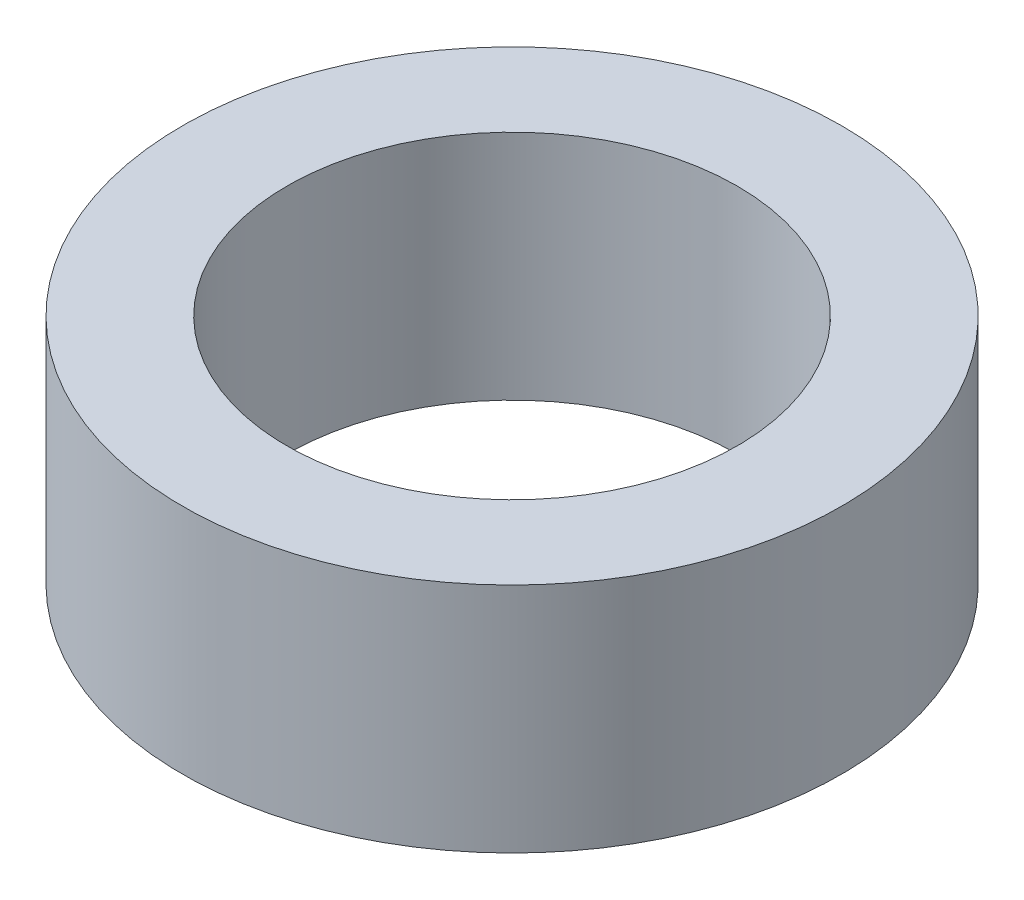
SolidWorks part; units mm, degrees
material "HDPE"
ref_plane "Piano frontale" through (0, 0, 0) normal (0, 0, 1) x (1, 0, 0)
ref_plane "Piano superiore" through (0, 0, 0) normal (0, 1, 0) x (1, 0, 0)
ref_plane "Piano destro" through (0, 0, 0) normal (1, 0, 0) x (0, 0, -1)
sketch "Schizzo1" plane through (0, 0, 0) normal (0, 0, 1) x (1, 0, 0)
  line L0 (-71, 50) -> (-48.5, 50)
  line L1 (-48.5, 50) -> (-48.5, 0)
  line L2 (-48.5, 0) -> (-71, 0)
  line L3 (-71, 0) -> (-71, 50)
  line L4 (0, 0) -> (0, 44.9066) construction
  point P7 (0, 44.9066)
  point P8 (0, 0)
  dimension "D1" = 142
  dimension "D2" = 97
  dimension "D3" = 50
revolve "Rivoluzione1" add sketch "Schizzo1" angle 360 about L4
